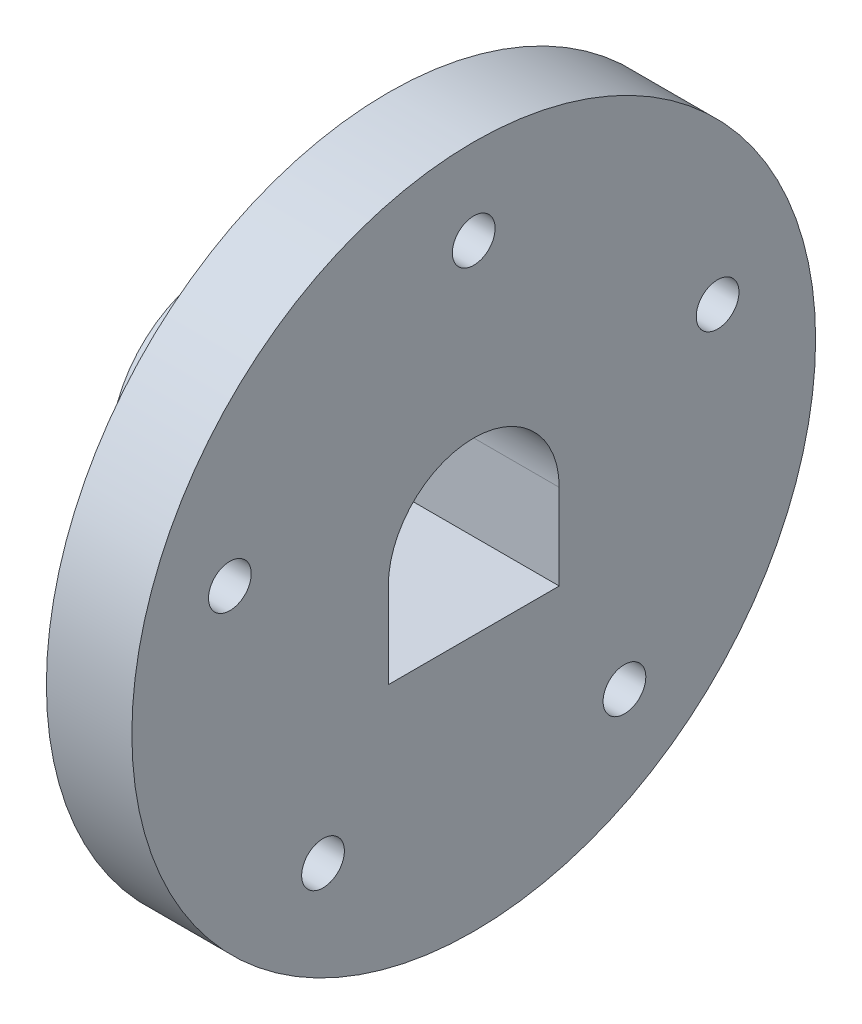
SolidWorks part; units mm, degrees
ref_plane "Front Plane" through (0, 0, 0) normal (0, 0, 1) x (1, 0, 0)
ref_plane "Top Plane" through (0, 0, 0) normal (0, 1, 0) x (1, 0, 0)
ref_plane "Right Plane" through (0, 0, 0) normal (1, 0, 0) x (0, 0, -1)
sketch "Sketch2" plane through (0, 0, 0) normal (1, 0, 0) x (0, 0, -1)
  circle A0 centre (0, 0) radius 4
  dimension "D1" = 8
extrude "Boss-Extrude1" add sketch "Sketch2" against normal blind 1
sketch "Sketch3" plane through (-1, 0, 0) normal (-1, 0, 0) x (0, 0, 1)
  circle A0 centre (0, 0) radius 1
  dimension "D1" = 2
sketch "Sketch4" plane through (0, 0, 0) normal (1, 0, 0) x (0, 0, -1)
  circle A0 centre (0, 0) radius 1
  dimension "D1" = 2
sketch "Sketch5" plane through (0, 0, 0) normal (1, 0, 0) x (0, 0, -1)
  line L0 (0, 0) -> (0, 4.8235) construction
  circle A0 centre (0, 3) radius 0.25
  dimension "D2" = 0.5
  dimension "D1" = 3
extrude "Cut-Extrude1" cut sketch "Sketch4" against normal blind 2.5
sketch "Sketch6" plane through (-1, 0, 0) normal (-1, 0, 0) x (0, 0, 1)
  line L0 (-1.25, 0) -> (-1.25, -1.25)
  line L1 (-1.25, -1.25) -> (1.25, -1.25)
  line L2 (1.25, -1.25) -> (1.25, 0)
  line L3 (-1, 0) -> (-1, -1)
  line L4 (-1, -1) -> (1, -1)
  line L5 (1, -1) -> (1, 0)
  circle A0 centre (0, 0) radius 1.25
  circle A1 centre (0, 0) radius 1 construction
  circle A2 centre (0, 0) radius 1
  circle M1 centre (0, 0) radius 1
  dimension "D1" = 2.5
extrude "Cut-Extrude2" cut sketch "Sketch5" against normal blind 2
pattern_circular "CirPattern1" count 5 over 360 about axis through (-2.5, 0, 0) along (1, 0, 0) of "Cut-Extrude2"
extrude "Cut-Extrude3" cut sketch "Sketch6" against normal through all contours L3 A0 L4 M1 | A0 L3 L4 | L4 A0 L5 M1 | A0 L4 L5 region at (-1, -0.9207, -0.9207) region at (-1, -0.7548, -0.7548) region at (-1, -0.7548, 0.7548) region at (-1, -0.9207, 0.9207)
extrude "Boss-Extrude2" add sketch "Sketch6<3>" along normal blind 2 contours A0 L4 L3 L0 L1 | A0 L3 L5 M1 | A0 L1 L2 L5 L4 | L4 A0 region at (-1, -0.4009, -1.2026) region at (-1, 1.218, 0) region at (-1, -0.625, 1.2323) region at (-1, -1.1009, 0)
sketch "Sketch6<3>" plane through (-1, 0, 0) normal (-1, 0, 0) x (0, 0, 1) same geometry as "Sketch6"
